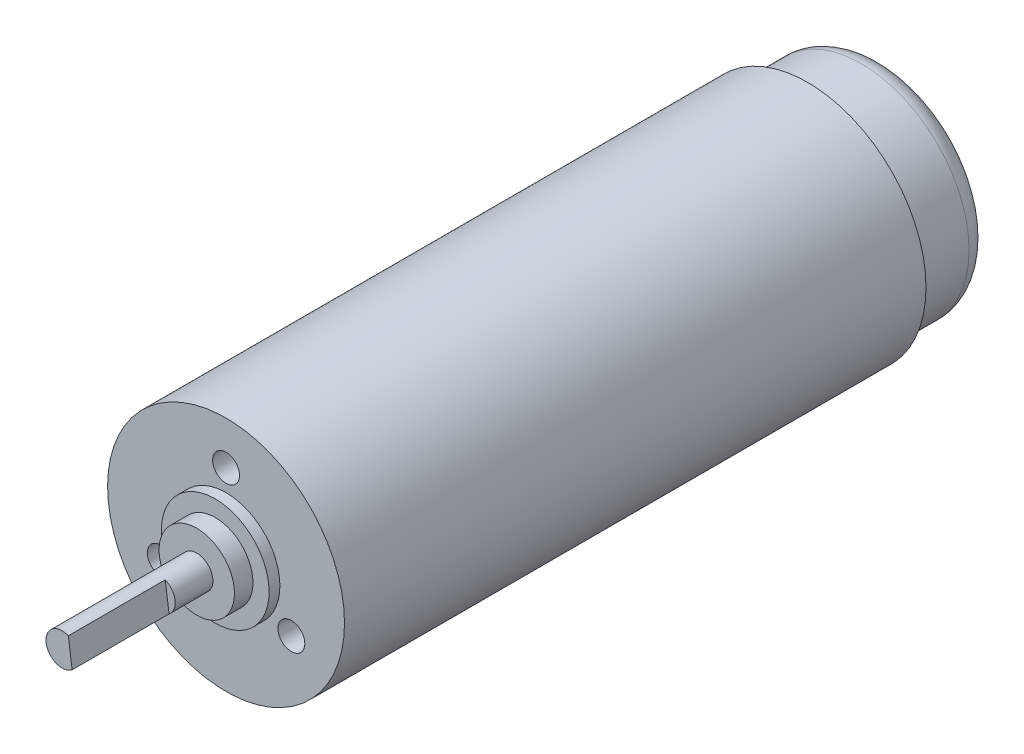
SolidWorks part; units mm, degrees
ref_plane "Front Plane" through (0, 0, 0) normal (0, 0, 1) x (1, 0, 0)
ref_plane "Top Plane" through (0, 0, 0) normal (0, 1, 0) x (1, 0, 0)
ref_plane "Right Plane" through (0, 0, 0) normal (1, 0, 0) x (0, 0, -1)
sketch "Sketch1" plane through (0, 0, 0) normal (0, 0, 1) x (1, 0, 0)
  line L0 (0, -0.0586) -> (0, 0)
  circle A0 centre (0, 0) radius 10
  dimension "D1" = 20
extrude "Boss-Extrude1" add sketch "Sketch1" along normal blind 7 contours A0 region at (-9.7172, 0, 0)
sketch "Sketch2" plane through (0, 0, 7) normal (0, 0, 1) x (1, 0, 0)
  circle A0 centre (0, 0) radius 11
  dimension "D1" = 22
extrude "Boss-Extrude2" add sketch "Sketch2" along normal blind 54
sketch "Sketch3" plane through (0, 0, 61) normal (0, 0, 1) x (1, 0, 0)
  circle A0 centre (0, 0) radius 5
  dimension "D1" = 10
extrude "Boss-Extrude4" add sketch "Sketch3" along normal blind 1 contours A0
sketch "Sketch5" plane through (0, 0, 62) normal (0, 0, 1) x (1, 0, 0)
  circle A0 centre (0, 0) radius 3.5
  dimension "D1" = 7
extrude "Boss-Extrude5" add sketch "Sketch5" along normal blind 1.72 contours A0
sketch "Sketch6" plane through (0, 0, 63.72) normal (0, 0, 1) x (1, 0, 0)
  circle A0 centre (0, 0) radius 1.5
  dimension "D1" = 3
extrude "Boss-Extrude6" add sketch "Sketch6" along normal blind 12.5 contours A0
sketch "Sketch17" plane through (0, 0, 76.22) normal (0, 0, 1) x (1, 0, 0)
  line L0 (0.5756, 1.3851) -> (0.9276, -1.1788)
  circle A0 centre (0, 0) radius 1.5 construction
extrude "Cut-Extrude1" cut sketch "Sketch17" against normal blind 9 and the other way through all
sketch "Sketch18" plane through (0, 0, 61) normal (0, 0, 1) x (1, 0, 0)
  circle A0 centre (0, 7) radius 1.25
  circle A1 centre (0, 0) radius 11 construction
  dimension "D1" = 7
  dimension "D2" = 2.5
extrude "Cut-Extrude2" cut sketch "Sketch18" against normal blind 9
pattern_circular "CirPattern1" count 3 over 360 about axis through (0, 0, 61) along (0, 0, 1) of "Cut-Extrude2"
fillet "Fillet1" radius 2 1 edges at (10, 0, 0)
